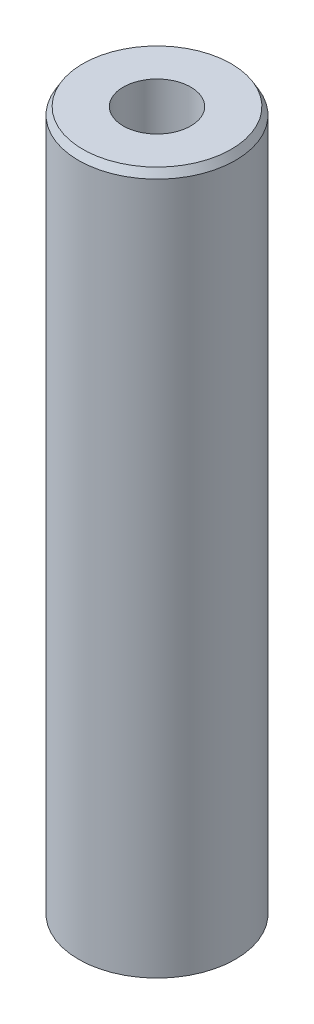
SolidWorks part; units mm, degrees
ref_plane "Front Plane" through (0, 0, 0) normal (0, 0, 1) x (1, 0, 0)
ref_plane "Top Plane" through (0, 0, 0) normal (0, 1, 0) x (1, 0, 0)
ref_plane "Right Plane" through (0, 0, 0) normal (1, 0, 0) x (0, 0, -1)
sketch "Sketch1" plane through (0, 0, 0) normal (0, 1, 0) x (1, 0, 0)
  circle A0 centre (0, 0) radius 10
  dimension "SHAFT_OD" = 20
extrude "Boss-Extrude1" add sketch "Sketch1" along normal blind 89.6439
sketch "Sketch2" plane through (0, 0, 0) normal (0, 1, 0) x (1, 0, 0)
  circle A0 centre (0, 0) radius 4.2997
  dimension "BORE_D" = 8.5994
extrude "Cut-Extrude1" cut sketch "Sketch2" along normal through all
chamfer "Chamfer1" distance 0.9469 angle 30 2 edges at (0, 89.6439, 10) (0, 0, 10) first distance on face at (0, 89.6439, 10) first distance on face at (0, 0, 4.2997)
